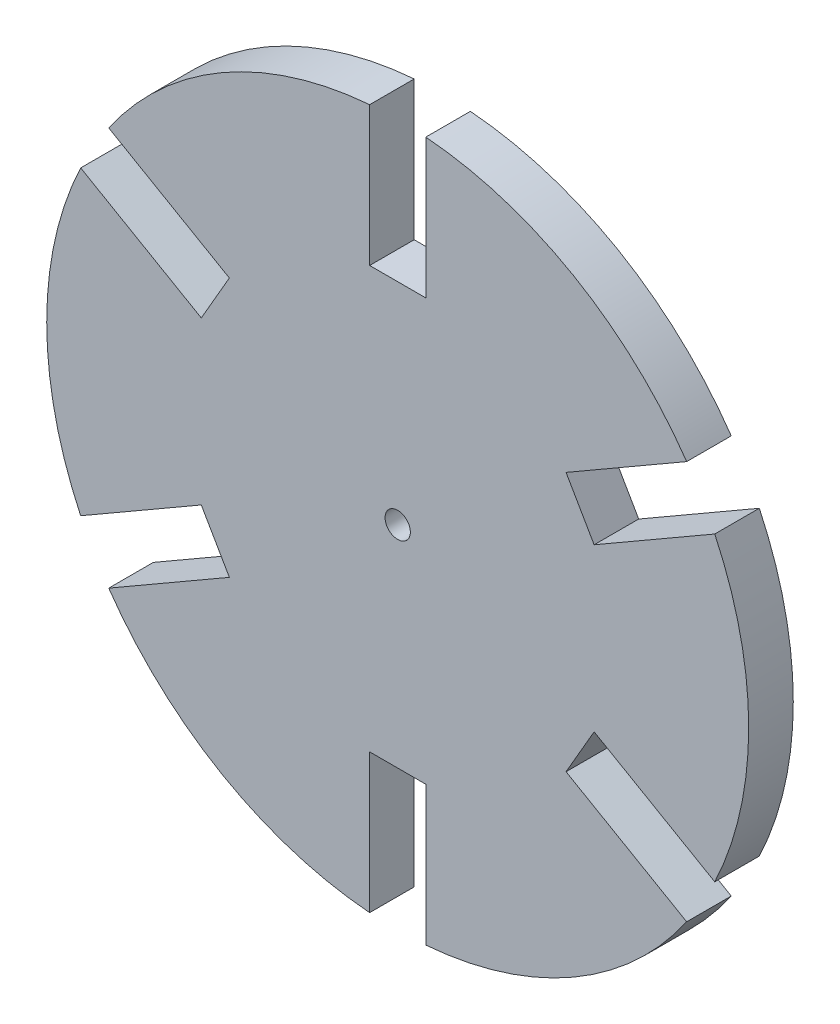
SolidWorks part; units mm, degrees
ref_plane "Front Plane" through (0, 0, 0) normal (0, 0, 1) x (1, 0, 0)
ref_plane "Top Plane" through (0, 0, 0) normal (0, 1, 0) x (1, 0, 0)
ref_plane "Right Plane" through (0, 0, 0) normal (1, 0, 0) x (0, 0, -1)
sketch "Sketch1" plane through (0, 0, 0) normal (0, 0, 1) x (1, 0, 0)
  circle A0 centre (0, 0) radius 25
  circle A1 centre (0, 0) radius 0.9
  dimension "D1" = 1.8
  dimension "D2" = 50
extrude "Boss-Extrude1" add sketch "Sketch1" along normal mid plane 3.175
sketch "Sketch2" plane through (0, 0, -1.5875) normal (0, 0, -1) x (-1, 0, 0)
  line L0 (0, 0) -> (0, 25) construction
  line L1 (2, 34.0448) -> (-2, 34.0448)
  line L2 (-2, 34.0448) -> (-2, 15)
  line L3 (-2, 15) -> (2, 15)
  line L4 (2, 15) -> (2, 34.0448)
  circle A0 centre (0, 0) radius 25 construction
  point P9 (0, 34.0448)
  dimension "D1" = 15
  dimension "D2" = 4
extrude "Cut-Extrude1" cut sketch "Sketch2" against normal up to body separate body
pattern_circular "CirPattern1" count 6 over 360 about axis through (0, 0, 1.5875) along (0, 0, 1) of "Cut-Extrude1"
